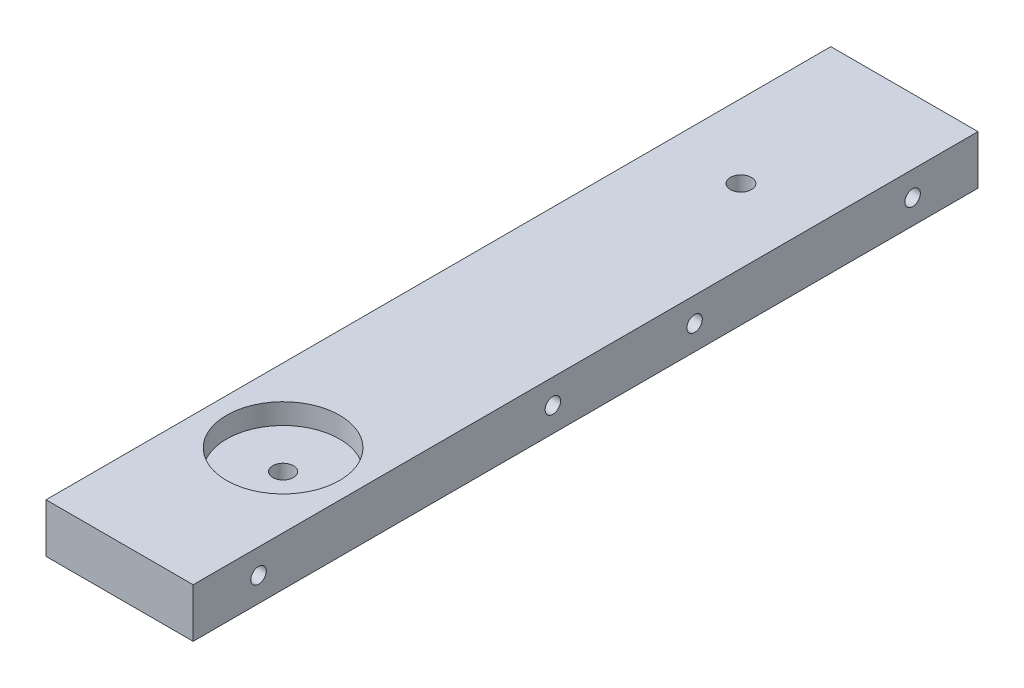
SolidWorks part; units mm, degrees
ref_plane "Front Plane" through (0, 0, 0) normal (0, 0, 1) x (1, 0, 0)
ref_plane "Top Plane" through (0, 0, 0) normal (0, 1, 0) x (1, 0, 0)
ref_plane "Right Plane" through (0, 0, 0) normal (1, 0, 0) x (0, 0, -1)
sketch "Sketch2" plane through (0, 0, 0) normal (0, 1, 0) x (1, 0, 0)
  line L0 (0, 0) -> (0, 152.4)
  line L1 (0, 152.4) -> (28.575, 152.4)
  line L2 (28.575, 152.4) -> (28.575, 0)
  line L3 (28.575, 0) -> (0, 0)
  dimension "D1" = 152.4
  dimension "D2" = 28.575
extrude "Boss-Extrude1" add sketch "Sketch2" along normal blind 9.525
sketch "Sketch3" plane through (0, 0, 0) normal (-1, 0, 0) x (0, 0, 1)
  line L3 (-152.4, 9.525) -> (0, 9.525) construction
  line L4 (-152.4, 9.525) -> (-152.4, 0) construction
  point P6 (-139.7, 4.7625)
  point P14 (-139.7, 4.7625)
  dimension "D1" = 4.7625
  dimension "D2" = 12.7
sketch "Sketch8" plane through (0, 0, 0) normal (-1, 0, 0) x (0, 0, 1)
  point P0 (-139.7, 4.7625)
hole_wizard "Ø3.0mm Dowel Hole1" positions "Sketch8" profile "Sketch9" hole size "Ø3.0" standard "ANSI Metric" end condition through all
sketch "Sketch9" plane through (0, 4.7625, -139.7) normal (0, 1, 0) x (0, 0, 1)
  line L0 (0, 0) -> (0, 28.575)
  line L1 (0, 28.575) -> (1.5, 28.575)
  line L2 (1.5, 28.575) -> (1.5, 0)
  line L5 (1.5, 0) -> (0, 0)
  line L11 (0, -6.35) -> (0, 107.95) construction
  dimension "Thru Hole Dia." = 3
  dimension "Thru Hole Depth" = 28.575
pattern_linear "LPattern1" count 4 spacing 42.3333 along (0, 0, 1) skipping (2, 0) of "Ø3.0mm Dowel Hole1"
sketch "Sketch12" plane through (0, 9.525, 0) normal (0, 1, 0) x (1, 0, 0)
  line L0 (28.575, 0) -> (28.575, 152.4) construction
  line L2 (0, 0) -> (28.575, 0) construction
  circle A1 centre (14.2875, 31.75) radius 10.975
  circle A2 centre (14.2875, 120.65) radius 2.05
  point P0 (14.2875, 120.65)
  point P1 (14.2875, 76.2)
  point P2 (14.2875, 31.75)
  dimension "D8" = 4.1
  dimension "D9" = 21.95
  dimension "D1" = 14.2875
  dimension "D2" = 14.2875
  dimension "D3" = 14.2875
  dimension "D4" = 76.2
  dimension "D5" = 44.45
  dimension "D6" = 44.45
sketch "Sketch13" plane through (0, 0, 0) normal (-1, 0, 0) x (0, 0, 1)
  line L2 (0, 9.525) -> (0, 0) construction
  line L3 (-152.4, 9.525) -> (0, 9.525) construction
  point P5 (-69.85, 4.7625)
  dimension "D1" = 69.85
  dimension "D2" = 4.7625
hole_wizard "Ø3.0mm Dowel Hole2" positions "Sketch13" profile "Sketch14" hole size "Ø3.0" standard "ANSI Metric" end condition through all
sketch "Sketch14" plane through (0, 4.7625, -69.85) normal (0, 1, 0) x (0, 0, 1)
  line L0 (0, 0) -> (0, 28.575)
  line L1 (0, 28.575) -> (1.5, 28.575)
  line L2 (1.5, 28.575) -> (1.5, 0)
  line L5 (1.5, 0) -> (0, 0)
  line L11 (0, -6.35) -> (0, 107.95) construction
  dimension "Thru Hole Dia." = 3
  dimension "Thru Hole Depth" = 28.575
extrude "Cut-Extrude1" cut sketch "Sketch12" against normal through all contours A2
extrude "Cut-Extrude2" cut sketch "Sketch12<4>" against normal blind 4 contours A1
sketch "Sketch12<4>" plane through (0, 9.525, 0) normal (0, 1, 0) x (1, 0, 0) same geometry as "Sketch12"
sketch "Sketch15" plane through (0, 5.525, 0) normal (0, 1, 0) x (1, 0, 0)
  circle A0 centre (14.2875, 31.75) radius 2
  dimension "D1" = 4
extrude "Cut-Extrude3" cut sketch "Sketch15" against normal through all
